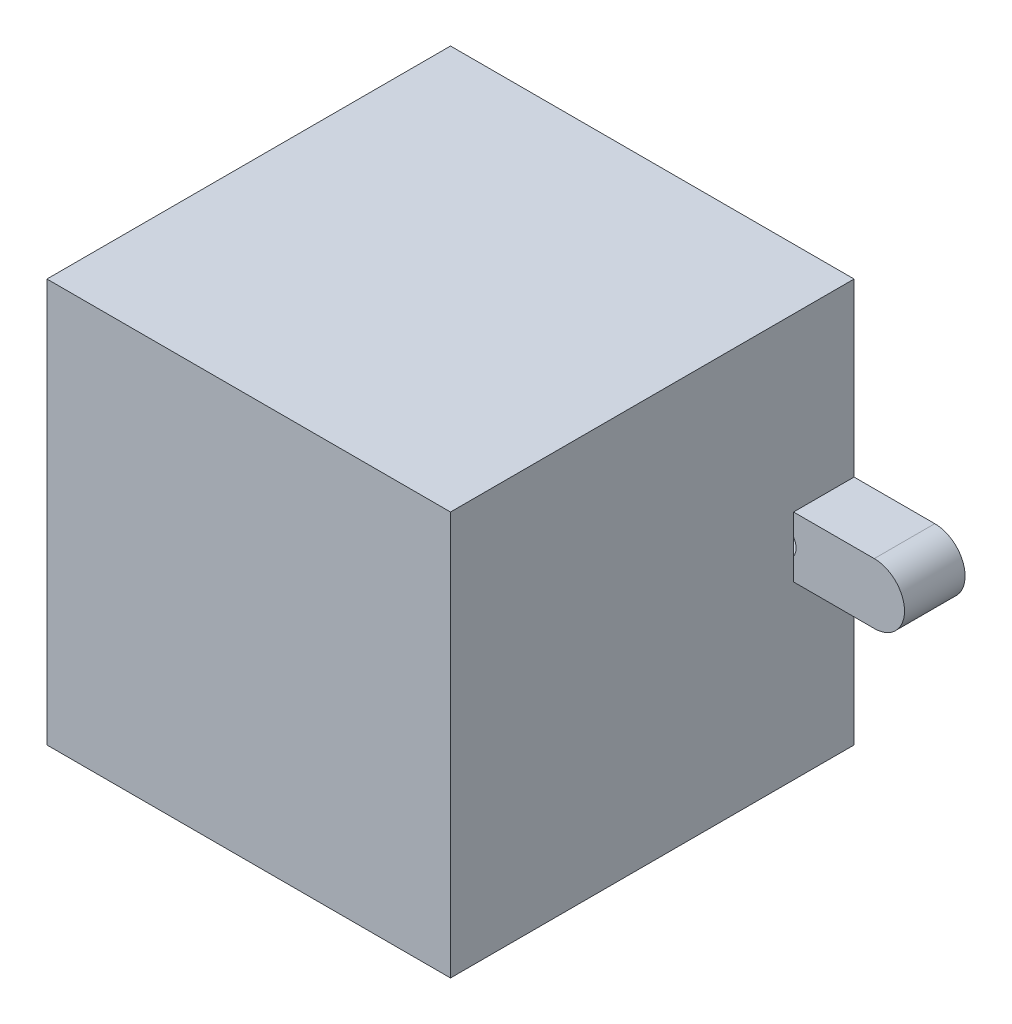
SolidWorks part; units mm, degrees
ref_plane "Front Plane" through (0, 0, 0) normal (0, 0, 1) x (1, 0, 0)
ref_plane "Top Plane" through (0, 0, 0) normal (0, 1, 0) x (1, 0, 0)
ref_plane "Right Plane" through (0, 0, 0) normal (1, 0, 0) x (0, 0, -1)
sketch "Sketch1" plane through (0, 0, 0) normal (0, 0, 1) x (1, 0, 0)
  line L1 (20, -20) -> (-20, -20)
  line L2 (20, -20) -> (20, 20)
  line L3 (20, 20) -> (-20, 20)
  line L4 (-20, -20) -> (-20, 20)
  line L5 (20, -20) -> (-20, 20) construction
  line L6 (20, 20) -> (-20, -20) construction
  line L7 (20, -3) -> (31, -3)
  line L9 (-20, 0) -> (-20, -3)
  line L10 (-20, -3) -> (-31, -3)
  line L11 (-31, -6) -> (-31, -3)
  line L12 (-20, -9) -> (-31, -9)
  line L13 (-20, -9) -> (-20, 0)
  line L15 (-31, -9) -> (-31, -6)
  line L16 (20, -3) -> (20, -9)
  line L17 (20, -9) -> (31, -9)
  line L18 (31, -3) -> (31, -9)
  point P0 (0, 0)
  dimension "D1" = 40
  dimension "D2" = 40
  dimension "D3" = 3
  dimension "D4" = 3
  dimension "D5" = 11
  dimension "D6" = 11
  dimension "D7" = 6
extrude "Boss-Extrude1" add sketch "Sketch1" along normal blind 40 contours L4 L1 L2 L3 region at (0, 0, 0)
sketch "Sketch2" plane through (0, 0, 0) normal (0, 0, -1) x (-1, 0, 0)
  line L1 (13.5, -13.5) -> (-13.5, -13.5)
  line L2 (13.5, -13.5) -> (13.5, 13.5)
  line L3 (13.5, 13.5) -> (-13.5, 13.5)
  line L4 (-13.5, -13.5) -> (-13.5, 13.5)
  line L5 (13.5, -13.5) -> (-13.5, 13.5) construction
  line L6 (13.5, 13.5) -> (-13.5, -13.5) construction
  point P0 (0, 0)
  dimension "D1" = 27
  dimension "D2" = 27
extrude "Cut-Extrude1" cut sketch "Sketch2" against normal blind 39
sketch "Sketch3" plane through (0, 0, 0) normal (0, 0, -1) x (-1, 0, 0)
  line L0 (20, -20) -> (20, 20) construction
  line L1 (-20, -20) -> (-20, 20) construction
  line L4 (-20, 0) -> (-20, 3)
  line L5 (-20, 3) -> (-31, 3)
  line L6 (-31, 0) -> (-31, 3)
  line L8 (-20, 0) -> (-20, -3)
  line L9 (-20, -3) -> (-31, -3)
  line L10 (-31, 0) -> (-31, -3)
  line L11 (20, 3) -> (31, 3)
  line L12 (20, 3) -> (20, -3)
  line L13 (20, -3) -> (31, -3)
  line L14 (31, 3) -> (31, -3)
  dimension "D1" = 3
  dimension "D2" = 3
  dimension "D3" = 11
  dimension "D4" = 6
  dimension "D5" = 11
extrude "Boss-Extrude3" add sketch "Sketch3" against normal blind 6
sketch "Sketch6" plane through (0, 0, 0) normal (0, 0, -1) x (-1, 0, 0)
  line L0 (-13.5, 13.5) -> (-13.5, -13.5) construction
  line L1 (-13.5, 2.0294) -> (-24, 2.0294)
  line L2 (-13.5, 2.0294) -> (-13.5, -1.9706)
  line L3 (-13.5, -1.9706) -> (-24, -1.9706)
  line L4 (-24, 2.0294) -> (-24, -1.9706)
  dimension "D1" = 10.5
  dimension "D2" = 4
extrude "Cut-Extrude2" cut sketch "Sketch6" against normal blind 4
sketch "Sketch7" plane through (0, 0, 0) normal (0, 0, -1) x (-1, 0, 0)
  line L0 (13.5, -13.5) -> (13.5, 13.5) construction
  line L1 (13.5, 1.9473) -> (24, 1.9473)
  line L2 (13.5, 1.9473) -> (13.5, -2.0527)
  line L3 (13.5, -2.0527) -> (24, -2.0527)
  line L4 (24, 1.9473) -> (24, -2.0527)
  dimension "D1" = 10.5
  dimension "D2" = 4
extrude "Cut-Extrude3" cut sketch "Sketch7" against normal blind 4
sketch "Sketch9" plane through (0, 0, 4) normal (0, 0, -1) x (-1, 0, 0)
  line L0 (-18.75, 2.0294) -> (-18.75, -1.9706)
  line L1 (-13.5, 2.0294) -> (-24, 2.0294) construction
  line L2 (-24, -1.9706) -> (-13.5, -1.9706) construction
  line L3 (18.75, 1.9473) -> (18.75, -2.0527)
  line L4 (24, 1.9473) -> (13.5, 1.9473) construction
  line L5 (13.5, -2.0527) -> (24, -2.0527) construction
  circle A0 centre (-18.75, 0.0294) radius 1.5
  circle A1 centre (18.75, -0.0527) radius 1.5
  dimension "D1" = 3
  dimension "D2" = 3
extrude "Cut-Extrude4" cut sketch "Sketch9" against normal blind 2 contours A0
sketch "Sketch10" plane through (0, 0, 4) normal (0, 0, -1) x (-1, 0, 0)
  line L0 (18.75, 1.9473) -> (18.75, -2.0527)
  line L1 (24, 1.9473) -> (13.5, 1.9473) construction
  line L2 (13.5, -2.0527) -> (24, -2.0527) construction
  circle A0 centre (18.75, -0.0527) radius 1.5
  dimension "D1" = 3
extrude "Cut-Extrude5" cut sketch "Sketch10" against normal blind 2 and the other way blind 1 contours A0
fillet "Fillet3" 2 edges at (31, 3, 3) (31, -3, 3) type full round first side face at (25.5, 3, 3) second side face at (25.5, -3, 3) middle face at (31, 0, 3)
fillet "Fillet4" 2 edges at (24, 2.0294, 2) (24, -1.9706, 2) type full round first side face at (18.75, 2.0294, 2) second side face at (18.75, -1.9706, 2) middle face at (24, 0.0294, 2)
fillet "Fillet6" 2 edges at (-31, 3, 3) (-31, -3, 3) type full round first side face at (-25.5, 3, 3) second side face at (-25.5, -3, 3) middle face at (-31, 0, 3)
fillet "Fillet7" 2 edges at (-24, 1.9473, 2) (-24, -2.0527, 2) type full round first side face at (-18.75, 1.9473, 2) second side face at (-18.75, -2.0527, 2) middle face at (-24, -0.0527, 2)
